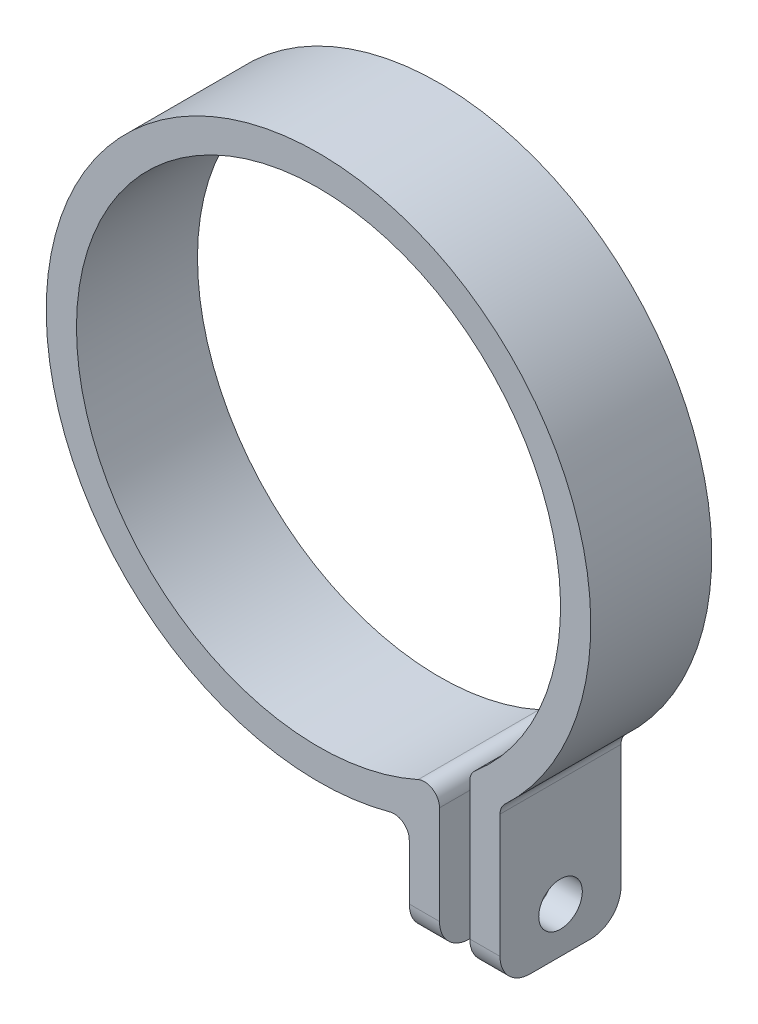
SolidWorks part; units mm, degrees
ref_plane "Front Plane" through (0, 0, 0) normal (0, 0, 1) x (1, 0, 0)
ref_plane "Top Plane" through (0, 0, 0) normal (0, 1, 0) x (1, 0, 0)
ref_plane "Right Plane" through (0, 0, 0) normal (1, 0, 0) x (0, 0, -1)
sketch "Sketch1" plane through (0, 0, 0) normal (0, 0, 1) x (1, 0, 0)
  line L0 (12.7, -21.997) -> (12.7, -38.1)
  line L1 (9.525, -26.9408) -> (9.525, -38.1)
  line L2 (9.525, -38.1) -> (12.7, -38.1)
  line L3 (15.875, -19.8279) -> (15.875, -38.1)
  line L4 (15.875, -38.1) -> (19.05, -38.1)
  line L5 (19.05, -38.1) -> (19.05, -21.2985)
  line L6 (-28.575, 0) -> (-28.575, -23.8501) construction
  arc A0 (15.875, -19.8279) -> (12.7, -21.997) centre (0, 0) ccw
  arc A1 (19.05, -21.2985) -> (9.525, -26.9408) centre (0, 0) ccw
  dimension "D1" = 50.8
  dimension "D2" = 3.175
  dimension "D3" = 3.175
  dimension "D4" = 3.175
  dimension "D5" = 3.175
  dimension "D6" = 38.1
  dimension "D7" = 41.275
extrude "Boss-Extrude1" add sketch "Sketch1" along normal mid plane 12.7
sketch "Sketch2" plane through (9.525, 0, 0) normal (-1, 0, 0) x (0, 0, 1)
  line L0 (6.35, -38.1) -> (-6.35, -38.1) construction
  circle A0 centre (0, -33.3375) radius 2.286
  dimension "D2" = 4.572
  dimension "D1" = 4.7625
extrude "Cut-Extrude1" cut sketch "Sketch2" against normal through all
fillet "Fillet1" radius 1.5875 4 edges at (9.525, -26.9408, 0) (19.05, -21.2985, 0) (12.7, -21.997, 0) (15.875, -19.8279, 0)
fillet "Fillet2" radius 3.175 4 edges at (11.1125, -38.1, -6.35) (17.4625, -38.1, -6.35) (17.4625, -38.1, 6.35) (11.1125, -38.1, 6.35)
